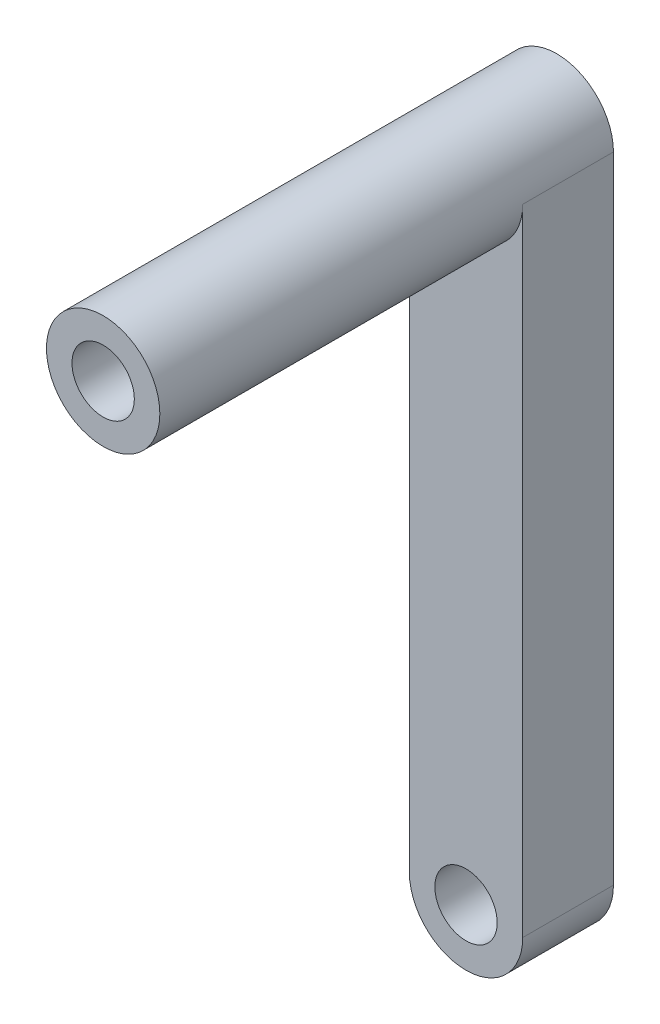
SolidWorks part; units mm, degrees
ref_plane "Front Plane" through (0, 0, 0) normal (0, 0, 1) x (1, 0, 0)
ref_plane "Top Plane" through (0, 0, 0) normal (0, 1, 0) x (1, 0, 0)
ref_plane "Right Plane" through (0, 0, 0) normal (1, 0, 0) x (0, 0, -1)
sketch "Sketch1" plane through (0, 0, 0) normal (0, 0, 1) x (1, 0, 0)
  line L0 (0, -10.1471) -> (0, 17.8529) construction
  line L1 (-2.5, -10.1471) -> (-2.5, 17.8529)
  line L2 (2.5, -10.1471) -> (2.5, 17.8529)
  arc A0 (-2.5, -10.1471) -> (2.5, -10.1471) centre (0, -10.1471) ccw
  arc A1 (2.5, 17.8529) -> (-2.5, 17.8529) centre (0, 17.8529) ccw
  circle A2 centre (0, 17.8529) radius 1.375
  circle A3 centre (0, -10.1471) radius 1.375
  arc A4 (-2.5, 17.8529) -> (2.5, 17.8529) centre (0, 17.8529) ccw
  point P3 (0, 3.8529)
  dimension "D3" = 2.75
  dimension "D4" = 2.75
  dimension "D6" = 2.75
  dimension "D1" = 28
  dimension "D2" = 28
  dimension "D5" = 5
extrude "Boss-Extrude3" add sketch "Sketch1" along normal blind 4 contours A3 A4 L1 A0 L2 region at (0, 2.4227, 0)
extrude "Boss-Extrude4" add sketch "Sketch1<6>" along normal blind 20 contours A1 A4 A2 region at (0, 20.2822, 0)
sketch "Sketch1<6>" plane through (0, 0, 0) normal (0, 0, 1) x (1, 0, 0) same geometry as "Sketch1"
